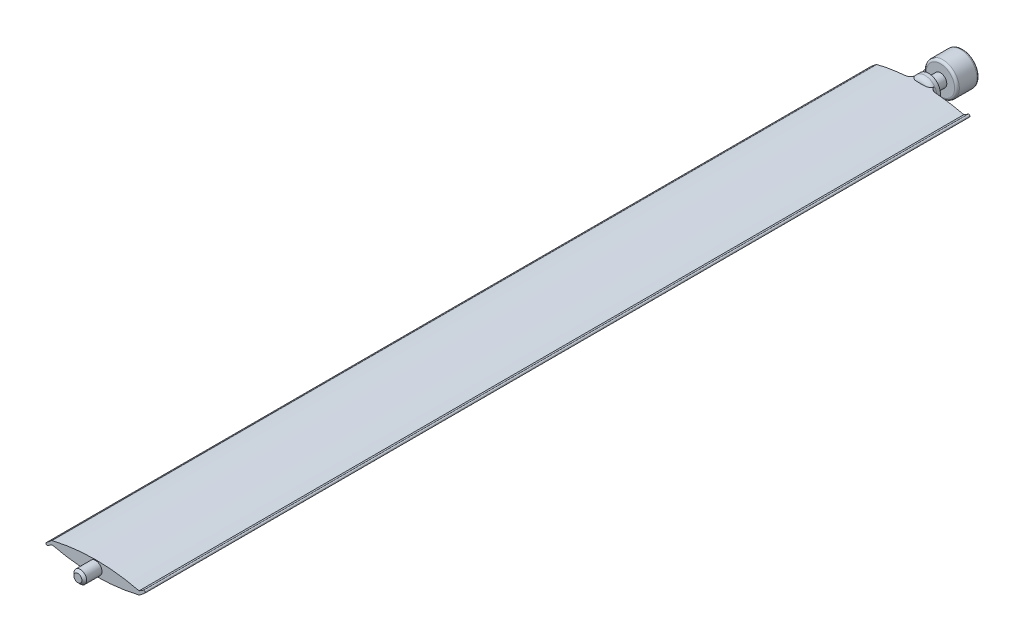
SolidWorks part; units mm, degrees
material "PVC 0.007 Plasticized"
ref_plane "Front Plane" through (0, 0, 0) normal (0, 0, 1) x (1, 0, 0)
ref_plane "Top Plane" through (0, 0, 0) normal (0, 1, 0) x (1, 0, 0)
ref_plane "Right Plane" through (0, 0, 0) normal (1, 0, 0) x (0, 0, -1)
sketch "Sketch1" plane through (0, 0, 0) normal (0, 0, 1) x (1, 0, 0)
  circle A0 centre (0, 14.4815) radius 1.35
  dimension "D1" = 2.7
extrude "Boss-Extrude1" add sketch "Sketch1" against normal blind 182.5
sketch "Sketch2" plane through (0, 0, -182.5) normal (0, 0, -1) x (-1, 0, 0)
  circle A0 centre (0, 14.4815) radius 3.5
  dimension "D1" = 7
extrude "Boss-Extrude2" add sketch "Sketch2" along normal blind 5.25
sketch "Sketch3" plane through (0, 0, -182.5) normal (0, 0, 1) x (1, 0, 0)
  circle A0 centre (0, 14.4815) radius 2.5
  dimension "D1" = 5
extrude "Boss-Extrude3" add sketch "Sketch3" along normal blind 1.75 from offset 2.5
chamfer "Chamfer1" distance 0.5 angle 45 1 edges at (1.35, 14.4815, 0)
fillet "Fillet1" radius 0.5 2 edges at (-3.5, 14.4815, -182.5) (-3.5, 14.4815, -187.75)
sketch "Sketch4" plane through (0, 0, -178.25) normal (0, 0, 1) x (1, 0, 0)
  line L0 (-9.5, 14.4815) -> (9.5, 14.4815) construction
  line L1 (0, 51.5724) -> (0, -22.6094) construction
  line L2 (0, 15.9815) -> (0, 12.9815) construction
  arc A0 (9.1953, 14.093) -> (9.1953, 14.87) centre (9.1, 14.4815) ccw
  arc A1 (-9.1953, 14.87) -> (-9.1953, 14.093) centre (-9.1, 14.4815) ccw
  arc A2 (9.1953, 14.87) -> (-9.1953, 14.87) centre (0, -22.6094) ccw
  arc A4 (-9.1953, 14.093) -> (9.1953, 14.093) centre (0, 51.5724) ccw
  dimension "0.8" = 0.8
  dimension "D1" = 19
  dimension "D2" = 3
extrude "Boss-Extrude4" add sketch "Sketch4" along normal blind 174.5
fillet "Fillet2" radius 1 2 edges at (0, 11.9815, -178.25) (0, 16.9815, -178.25)
fillet "Fillet3" radius 1 2 edges at (-2.5, 14.4815, -178.25) (2.5, 14.4815, -178.25)
ref_plane "Plane1" through (0, 0, -187.25) normal (0, 0, 1) x (1, 0, 0)
sketch "Sketch5" plane through (0, 0, -187.25) normal (0, 0, 1) x (1, 0, 0)
  line L0 (0, 14.4815) -> (0, 17.9815) construction
  line L1 (0, 14.4815) -> (-5.6569, 8.8246) construction
  line L2 (-7.5402, 10.2302) -> (-2.8049, 16.5749)
  line L3 (-4.2513, 6.9413) -> (2.0934, 11.6766)
  arc A0 (2.0934, 11.6766) -> (-2.8049, 16.5749) centre (0, 14.4815) ccw
  circle A1 centre (0, 14.4815) radius 3.5 construction
  arc A2 (-7.5402, 10.2302) -> (-4.2513, 6.9413) centre (-5.6569, 8.8246) ccw
  dimension "D3" = 4.7
  dimension "D1" = 225
  dimension "D2" = 8
extrude "Boss-Extrude5" add sketch "Sketch5" along normal blind 1.5
sketch "Sketch6" plane through (0, 0, -185.75) normal (0, 0, 1) x (1, 0, 0)
  circle A0 centre (-5.6569, 8.8246) radius 1.5
  dimension "D1" = 3
extrude "Boss-Extrude6" add sketch "Sketch6" along normal blind 2
sketch "Sketch7" plane through (0, 0, -183.75) normal (0, 0, 1) x (1, 0, 0)
  circle A0 centre (-5.6569, 8.8246) radius 2
  dimension "D1" = 4
extrude "Boss-Extrude7" add sketch "Sketch7" along normal blind 1
chamfer "Chamfer2" distance 0.75 angle 45 1 edges at (-3.6569, 8.8246, -182.75)
sketch "Sketch8" plane through (0, 0, -182.75) normal (0, 0, 1) x (1, 0, 0)
  line L1 (-3.4069, 8.3246) -> (-7.9069, 8.3246)
  line L2 (-3.4069, 8.3246) -> (-3.4069, 9.3246)
  line L3 (-3.4069, 9.3246) -> (-7.9069, 9.3246)
  line L4 (-7.9069, 8.3246) -> (-7.9069, 9.3246)
  line L5 (-3.4069, 8.3246) -> (-7.9069, 9.3246) construction
  line L6 (-3.4069, 9.3246) -> (-7.9069, 8.3246) construction
  circle A0 centre (-5.6569, 8.8246) radius 2.25 construction
  point P0 (-5.6569, 8.8246)
  dimension "D1" = 1
extrude "Cut-Extrude1" cut sketch "Sketch8" against normal blind 2
fillet "Fillet4" radius 0.5 3 edges at (-1.0789, 9.309, -187.25) (-7.3186, 7.1629, -187.25) (-5.1725, 13.4026, -187.25)
sketch "Sketch11" plane through (0, 0, -3.75) normal (0, 0, 1) x (1, 0, 0)
  line L0 (0, 14.4815) -> (-10.5, 14.4815) construction
  line L1 (-9.5, 14.4815) -> (-10.25, 13.7315) construction
  line L2 (-10.5, 13.7315) -> (-10.5, 14.4815) construction
  line L3 (-10.4086, 13.9247) -> (-9.3538, 14.7907)
  line L4 (-10.118, 13.5192) -> (-9.1953, 14.093)
  line L5 (-9.3538, 14.7907) -> (-9.1953, 14.093)
  line L6 (0, 14.4815) -> (0, 15.3315) construction
  line L7 (10.118, 13.5192) -> (9.1953, 14.093) construction
  line L8 (9.3538, 14.7907) -> (9.1953, 14.093) construction
  line L9 (10.4086, 13.9247) -> (9.3538, 14.7907) construction
  line L10 (10.118, 15.4438) -> (9.1953, 14.87)
  line L11 (10.4086, 15.0383) -> (9.3538, 14.1723)
  line L12 (9.3538, 14.1723) -> (9.1953, 14.87)
  line L13 (10.5, 13.7315) -> (10.5, 14.4815) construction
  arc A0 (-9.1953, 14.87) -> (-9.1953, 14.093) centre (-9.1, 14.4815) ccw construction
  arc A1 (-10.4086, 13.9247) -> (-10.118, 13.5192) centre (-10.25, 13.7315) ccw
  circle A2 centre (0, 14.4815) radius 0.85 construction
  arc A3 (10.4086, 13.9247) -> (10.118, 13.5192) centre (10.25, 13.7315) cw construction
  arc A4 (10.4086, 15.0383) -> (10.118, 15.4438) centre (10.25, 15.2315) ccw
  dimension "D2" = 0.5
  dimension "D1" = 45
  dimension "D3" = 21
extrude "Boss-Extrude8" add sketch "Sketch11" against normal up to surface (174.5 mm away) up to face at (-6.3641, 14.4815, -178.25)
sketch "Sketch12" plane through (0, 0, -187.75) normal (0, 0, -1) x (-1, 0, 0)
  line L1 (-3.5, 17.9815) -> (8.0069, 17.9815)
  line L2 (-3.5, 17.9815) -> (-3.5, 6.4746)
  line L3 (-3.5, 6.4746) -> (8.0069, 6.4746)
  line L4 (8.0069, 17.9815) -> (8.0069, 6.4746)
  arc A0 (4.2513, 6.9413) -> (7.5402, 10.2302) centre (5.6569, 8.8246) ccw construction
  arc A1 (-3.2228, 15.8467) -> (-3.2228, 13.1163) centre (0, 14.4815) ccw construction
  arc A2 (1.326, 17.7206) -> (-3.2391, 13.1555) centre (0, 14.4815) ccw construction
extrude "Cut-Extrude2" cut sketch "Sketch12" against normal up to vertex (1 mm away) up to point (-7.5402, 10.2302, -186.75)
sketch "Sketch13" plane through (0, 0, -186.75) normal (0, 0, -1) x (-1, 0, 0)
  line L4 (-2.0934, 11.6766) -> (4.2513, 6.9413)
  line L5 (7.5402, 10.2302) -> (2.8049, 16.5749)
  line L6 (-2.0934, 11.6766) -> (4.2513, 6.9413)
  line L7 (7.5402, 10.2302) -> (2.8049, 16.5749)
  arc A4 (2.8049, 16.5749) -> (-2.0934, 11.6766) centre (0, 14.4815) ccw
  arc A5 (4.2513, 6.9413) -> (7.5402, 10.2302) centre (5.6569, 8.8246) ccw
  arc A6 (2.8049, 16.5749) -> (-2.0934, 11.6766) centre (0, 14.4815) ccw
  arc A7 (4.2513, 6.9413) -> (7.5402, 10.2302) centre (5.6569, 8.8246) ccw
  dimension "D1" = 0
extrude "Boss-Extrude9" add sketch "Sketch13" along normal blind 0.5
fillet "Fillet5" radius 0.5 4 edges at (-7.3186, 7.1629, -187.25) (-1.0789, 9.309, -187.25) (2.4749, 16.9564, -187.25) (-5.1725, 13.4026, -187.25)
